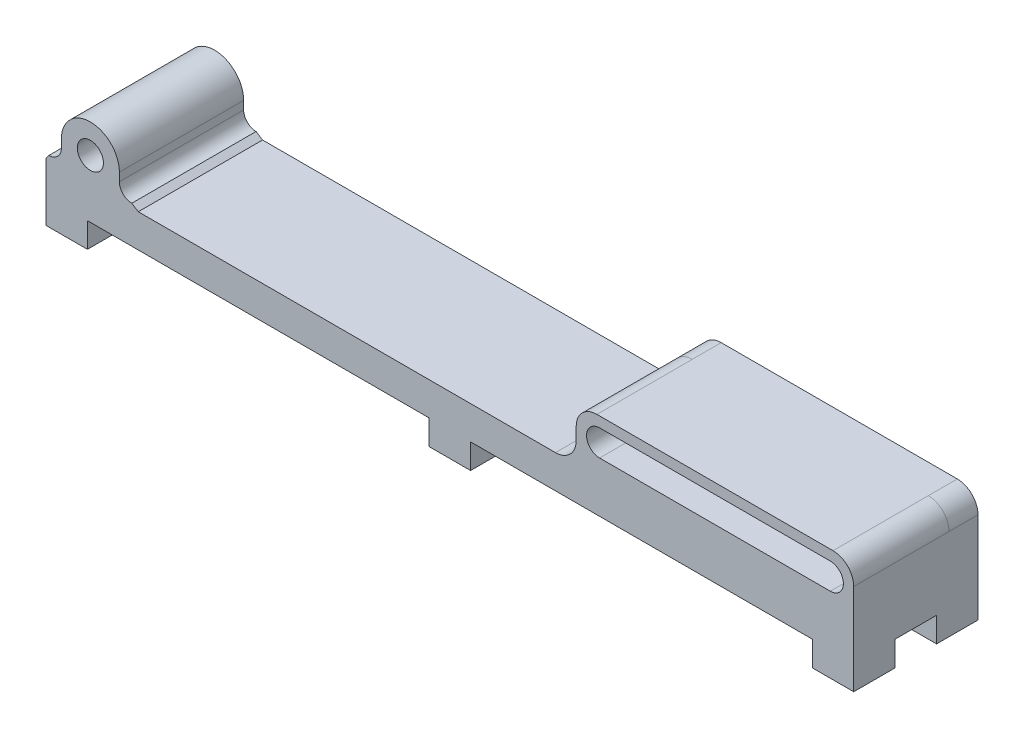
SolidWorks part; units mm, degrees
ref_plane "Front Plane" through (0, 0, 0) normal (0, 0, 1) x (1, 0, 0)
ref_plane "Top Plane" through (0, 0, 0) normal (0, 1, 0) x (1, 0, 0)
ref_plane "Right Plane" through (0, 0, 0) normal (1, 0, 0) x (0, 0, -1)
sketch "Sketch1" plane through (0, 0, 0) normal (0, 1, 0) x (1, 0, 0)
  line L1 (0, 0) -> (195, 0)
  line L2 (0, 0) -> (0, 30)
  line L3 (0, 30) -> (195, 30)
  line L4 (195, 0) -> (195, 30)
  dimension "D1" = 195
  dimension "D2" = 30
extrude "Boss-Extrude1" add sketch "Sketch1" along normal blind 8
sketch "Sketch2" plane through (0, 8, 0) normal (0, 1, 0) x (1, 0, 0)
  line L0 (195, 30) -> (0, 30) construction
  line L1 (4.7153, 30) -> (16.7153, 30)
  line L2 (4.7153, 30) -> (4.7153, 0)
  line L3 (4.7153, 0) -> (16.7153, 0)
  line L4 (16.7153, 30) -> (16.7153, 0)
  line L5 (0, 0) -> (195, 0) construction
  dimension "D1" = 12
extrude "Boss-Extrude2" add sketch "Sketch2" along normal blind 12
sketch "Sketch4" plane through (0, 0, -30) normal (0, 0, -1) x (-1, 0, 0)
  line L0 (-16.7153, 20) -> (-4.7153, 20) construction
  line L1 (-4.7153, 20) -> (-4.7153, 8) construction
  circle A0 centre (-10.7153, 14) radius 3.15
  dimension "D1" = 6
  dimension "D3" = 6.3
  dimension "D2" = 6
extrude "Cut-Extrude1" cut sketch "Sketch4" against normal through all
fillet "Fillet1" radius 4 2 edges at (4.7153, 8, -15) (16.7153, 8, -15)
fillet "Fillet2" radius 6 2 edges at (4.7153, 20, -15) (16.7153, 20, -15)
sketch "Sketch11" plane through (0, 0, -30) normal (0, 0, -1) x (-1, 0, 0)
  line L0 (-16.7153, 14) -> (-16.7153, 12) construction
  line L2 (-4.7153, 14) -> (-4.7153, 12) construction
  line L3 (-16.7153, 14) -> (-16.7153, 12)
  line L4 (-4.7153, 14) -> (-4.7153, 12)
  line L5 (-17.7153, 14) -> (-17.7153, 12)
  line L6 (-3.7153, 14) -> (-3.7153, 12)
  line L7 (-20.7153, 9) -> (-22.2788, 8)
  line L8 (-20.7153, 8) -> (-195, 8) construction
  line L9 (-22.2788, 8) -> (-20.7153, 8)
  line L10 (-0.7153, 9) -> (0, 8)
  line L11 (0, 8) -> (-0.7153, 8)
  arc A4 (-4.7153, 14) -> (-10.7153, 20) centre (-10.7153, 14) ccw construction
  arc A5 (-10.7153, 20) -> (-16.7153, 14) centre (-10.7153, 14) ccw construction
  arc A6 (-20.7153, 8) -> (-16.7153, 12) centre (-20.7153, 12) ccw construction
  arc A7 (-4.7153, 12) -> (-0.7153, 8) centre (-0.7153, 12) ccw construction
  arc A8 (-20.7153, 8) -> (-16.7153, 12) centre (-20.7153, 12) ccw
  arc A9 (-4.7153, 12) -> (-0.7153, 8) centre (-0.7153, 12) ccw
  arc A10 (-4.7153, 14) -> (-10.7153, 20) centre (-10.7153, 14) ccw
  arc A11 (-10.7153, 20) -> (-16.7153, 14) centre (-10.7153, 14) ccw
  arc A12 (-20.7153, 9) -> (-17.7153, 12) centre (-20.7153, 12) ccw
  arc A13 (-10.7153, 21) -> (-17.7153, 14) centre (-10.7153, 14) ccw
  arc A14 (-3.7153, 14) -> (-10.7153, 21) centre (-10.7153, 14) ccw
  arc A15 (-3.7153, 12) -> (-0.7153, 9) centre (-0.7153, 12) ccw
  dimension "D1" = 1
extrude "Boss-Extrude4" add sketch "Sketch11" against normal up to surface (30 mm away) up to face at (7.5653, 14, 0)
sketch "Sketch15" plane through (0, 8, 0) normal (0, 1, 0) x (1, 0, 0)
  line L0 (195, 15) -> (22.2788, 15) construction
  line L1 (195, 30) -> (128, 30)
  line L2 (195, 30) -> (195, 23)
  line L3 (195, 23) -> (128, 23)
  line L4 (128, 30) -> (128, 23)
  line L5 (195, 0) -> (195, 30) construction
  line L6 (22.2788, 0) -> (22.2788, 30) construction
  line L7 (195, 7) -> (128, 7)
  line L8 (128, 0) -> (128, 7)
  line L9 (195, 0) -> (128, 0)
  line L10 (195, 0) -> (195, 7)
  dimension "D1" = 7
  dimension "D2" = 67
extrude "Boss-Extrude6" add sketch "Sketch15" along normal blind 13
sketch "Sketch16" plane through (0, 0, -30) normal (0, 0, -1) x (-1, 0, 0)
  line L0 (-195, 21) -> (-195, 0) construction
  line L1 (-192.5, 18.5) -> (-130.5, 18.5)
  line L2 (-192.5, 18.5) -> (-192.5, 12.2)
  line L3 (-192.5, 12.2) -> (-130.5, 12.2)
  line L4 (-130.5, 18.5) -> (-130.5, 12.2)
  line L5 (-128, 21) -> (-128, 8) construction
  line L6 (-195, 21) -> (-128, 21) construction
  dimension "D1" = 2.5
  dimension "D2" = 2.5
  dimension "D3" = 6.3
  dimension "D4" = 2.5
extrude "Cut-Extrude4" cut sketch "Sketch16" against normal through all
fillet "Fillet6" radius 5 2 edges at (195, 21, -26.5) (128, 21, -26.5)
fillet "Fillet7" radius 5 1 edges at (128, 8, -26.5)
sketch "Sketch17" plane through (0, 0, 0) normal (0, -1, 0) x (1, 0, 0)
  line L0 (0, 0) -> (195, 0) construction
  line L1 (92.5, 0) -> (102.5, 0)
  line L2 (92.5, 0) -> (92.5, -30)
  line L3 (92.5, -30) -> (102.5, -30)
  line L4 (102.5, 0) -> (102.5, -30)
  line L5 (195, -30) -> (0, -30) construction
  line L6 (0, -30) -> (0, 0) construction
  dimension "D1" = 10
  dimension "D2" = 92.5
extrude "Boss-Extrude7" add sketch "Sketch17" along normal blind 6
fillet "Fillet8" radius 3.15 4 edges at (192.5, 18.5, -3.5) (192.5, 12.2, -3.5) (130.5, 18.5, -3.5) (130.5, 12.2, -3.5)
fillet "Fillet9" radius 5 1 edges at (128, 8, -3.5)
sketch "Sketch20" plane through (0, 0, -23) normal (0, 0, 1) x (1, 0, 0)
  line L2 (133.65, 12.2) -> (189.35, 12.2)
  line L3 (189.35, 18.5) -> (133.65, 18.5)
  line L4 (133.65, 12.2) -> (189.35, 12.2)
  line L5 (189.35, 18.5) -> (133.65, 18.5)
  line L18 (195, 0) -> (195, 21)
  line L19 (195, 21) -> (128, 21)
  line L20 (128, 21) -> (128, 13)
  line L21 (123, 8) -> (22.2788, 8)
  line L22 (22.2788, 8) -> (20.7153, 9)
  line L23 (17.7153, 12) -> (17.7153, 14)
  line L24 (3.7153, 14) -> (3.7153, 12)
  line L25 (0.7153, 9) -> (0, 8)
  line L26 (0, 8) -> (0, 0)
  line L27 (0, 0) -> (92.5, 0)
  line L28 (92.5, 0) -> (92.5, -6)
  line L29 (92.5, -6) -> (102.5, -6)
  line L30 (102.5, -6) -> (102.5, 0)
  line L31 (102.5, 0) -> (195, 0)
  line L32 (195, 0) -> (195, 21)
  line L33 (195, 21) -> (128, 21)
  line L34 (128, 21) -> (128, 13)
  line L35 (123, 8) -> (22.2788, 8)
  line L36 (22.2788, 8) -> (20.7153, 9)
  line L37 (17.7153, 12) -> (17.7153, 14)
  line L38 (3.7153, 14) -> (3.7153, 12)
  line L39 (0.7153, 9) -> (0, 8)
  line L40 (0, 8) -> (0, 0)
  line L41 (0, 0) -> (92.5, 0)
  line L42 (92.5, 0) -> (92.5, -6)
  line L43 (92.5, -6) -> (102.5, -6)
  line L44 (102.5, -6) -> (102.5, 0)
  line L45 (102.5, 0) -> (195, 0)
  circle A1 centre (10.7153, 14) radius 3.15
  circle A2 centre (10.7153, 14) radius 3.15
  arc A6 (130.5, 15.35) -> (133.65, 12.2) centre (133.65, 15.35) ccw
  arc A7 (133.65, 18.5) -> (130.5, 15.35) centre (133.65, 15.35) ccw
  arc A8 (192.5, 15.35) -> (189.35, 18.5) centre (189.35, 15.35) ccw
  arc A9 (189.35, 12.2) -> (192.5, 15.35) centre (189.35, 15.35) ccw
  arc A10 (130.5, 15.35) -> (133.65, 12.2) centre (133.65, 15.35) ccw
  arc A11 (133.65, 18.5) -> (130.5, 15.35) centre (133.65, 15.35) ccw
  arc A12 (192.5, 15.35) -> (189.35, 18.5) centre (189.35, 15.35) ccw
  arc A13 (189.35, 12.2) -> (192.5, 15.35) centre (189.35, 15.35) ccw
  arc A18 (123, 8) -> (128, 13) centre (123, 13) ccw
  arc A19 (17.7153, 12) -> (20.7153, 9) centre (20.7153, 12) ccw
  arc A20 (17.7153, 14) -> (3.7153, 14) centre (10.7153, 14) ccw
  arc A21 (0.7153, 9) -> (3.7153, 12) centre (0.7153, 12) ccw
  arc A24 (123, 8) -> (128, 13) centre (123, 13) ccw
  arc A25 (17.7153, 12) -> (20.7153, 9) centre (20.7153, 12) ccw
  arc A26 (17.7153, 14) -> (3.7153, 14) centre (10.7153, 14) ccw
  arc A27 (0.7153, 9) -> (3.7153, 12) centre (0.7153, 12) ccw
  dimension "D1" = 0
  dimension "D2" = 0
  dimension "D3" = 0
extrude "Boss-Extrude8" add sketch "Sketch20" along normal up to surface (16 mm away) up to face at (161.5, 15.35, -7)
sketch "Sketch21" plane through (0, 0, 0) normal (0, -1, 0) x (-1, 0, 0)
  line L0 (-92.5, 30) -> (0, 30) construction
  line L1 (0, 0) -> (-10, 0)
  line L2 (0, 0) -> (0, 30)
  line L3 (0, 30) -> (-10, 30)
  line L4 (-10, 0) -> (-10, 30)
  line L5 (-195, 30) -> (-102.5, 30) construction
  line L7 (-195, 0) -> (-195, 30)
  line L8 (-195, 30) -> (-185, 30)
  line L9 (-185, 0) -> (-185, 30)
  line L10 (-195, 0) -> (-185, 0)
  dimension "D1" = 10
  dimension "D2" = 10
extrude "Boss-Extrude9" add sketch "Sketch21" along normal blind 6
sketch "Sketch22" plane through (0, -6, 0) normal (0, -1, 0) x (-1, 0, 0)
  line L0 (0, 0) -> (0, 30) construction
  line L1 (0, 10) -> (-10, 10)
  line L2 (0, 10) -> (0, 20)
  line L3 (0, 20) -> (-10, 20)
  line L4 (-10, 10) -> (-10, 20)
  line L5 (-10, 30) -> (-10, 0) construction
  line L6 (0, 30) -> (-10, 30) construction
  line L7 (-92.5, 0) -> (-92.5, 30) construction
  line L8 (-92.5, 10) -> (-102.5, 10)
  line L9 (-92.5, 10) -> (-92.5, 20)
  line L10 (-92.5, 20) -> (-102.5, 20)
  line L11 (-102.5, 10) -> (-102.5, 20)
  line L12 (-102.5, 30) -> (-102.5, 0) construction
  line L13 (-185, 0) -> (-185, 30) construction
  line L14 (-185, 10) -> (-195, 10)
  line L15 (-185, 10) -> (-185, 20)
  line L16 (-185, 20) -> (-195, 20)
  line L17 (-195, 10) -> (-195, 20)
  line L18 (-195, 30) -> (-195, 0) construction
  dimension "D1" = 10
  dimension "D2" = 10
extrude "Cut-Extrude5" cut sketch "Sketch22" against normal blind 6
fillet "Fillet10" radius 5 2 edges at (128, 21, -11.5) (195, 21, -11.5)
fillet "Fillet11" radius 3.15 4 edges at (130.5, 18.5, -26.5) (130.5, 12.2, -26.5) (192.5, 12.2, -26.5) (192.5, 18.5, -26.5)
equation "\"7.5o\"=7.56878"
